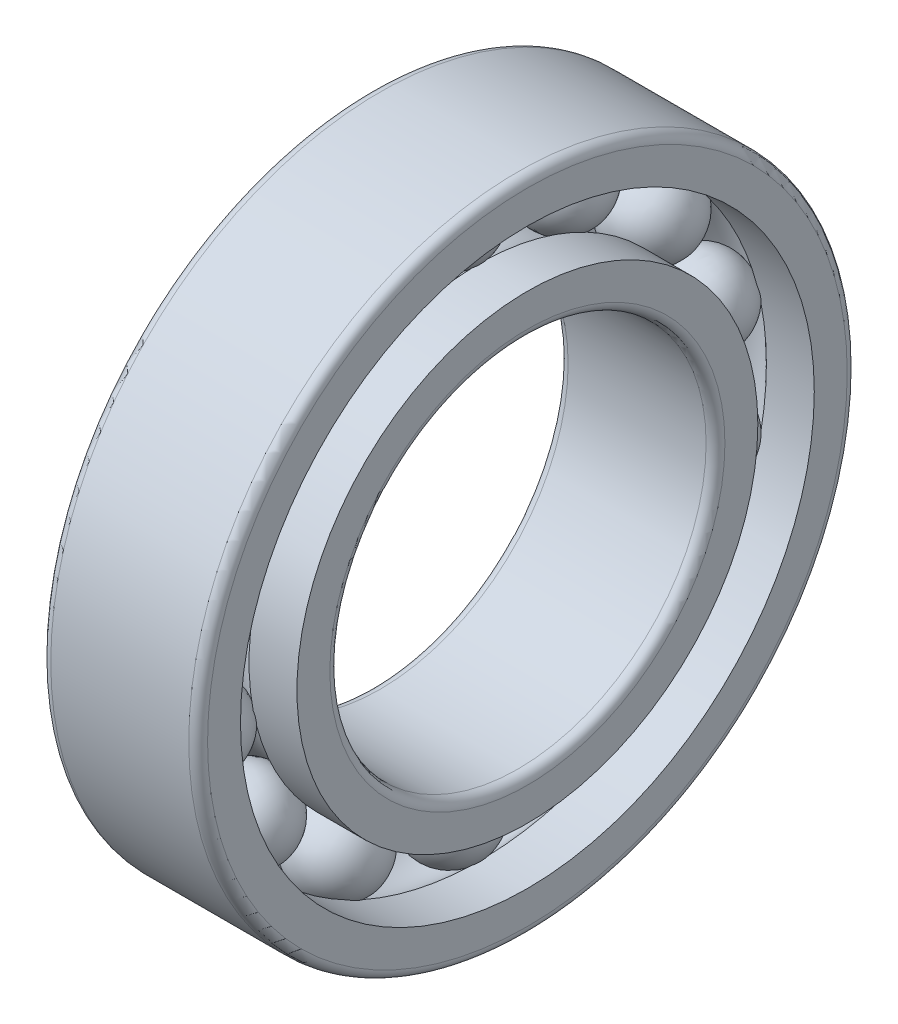
SolidWorks part; units mm, degrees
ref_plane "Plane1" through (0, 0, 0) normal (0, 0, 1) x (1, 0, 0)
ref_plane "Plane2" through (0, 0, 0) normal (0, 1, 0) x (1, 0, 0)
ref_plane "Plane3" through (0, 0, 0) normal (1, 0, 0) x (0, 0, -1)
sketch "Clipboard" plane through (0, 0, 0) normal (0, 0, 1) x (1, 0, 0)
  line L0 (-10, 0) -> (10, 0) construction
  line L1 (0, 0) -> (21.6965, -5.4095)
  line L2 (0, 0) -> (8.0049, 1.9959)
  line L3 (0, 0) -> (21.6965, -5.4095)
  line L4 (0, 0) -> (-22.3573, -0.3902)
  dimension "BallCLRad" = 8.25
sketch "CagSpiSke" plane through (0, 0, 0) normal (0, 0, 1) x (1, 0, 0)
  line L0 (0.135, 8.025) -> (0.135, 8.475)
  line L1 (0.135, 8.475) -> (-0.135, 8.475)
  line L2 (-0.135, 8.475) -> (-0.135, 8.025)
  line L3 (-0.135, 8.025) -> (0.135, 8.025)
  line L4 (-20.6375, 0) -> (20.6375, 0) construction
  line L5 (0, 0) -> (0, 23.7692) construction
  dimension "OD" = 16.95
  dimension "ID" = 16.05
revolve "CageSpine" add sketch "CagSpiSke" angle 0.001 about L4 reverse direction yes
ref_axis "Axis1" through (-50, 0, 0) along (1, 0, 0)
sketch "CagBalSke" plane through (0, 0, 0) normal (0, 0, 1) x (1, 0, 0)
  line L0 (-1.485, 8.25) -> (1.485, 8.25)
  line L1 (-1.905, 8.25) -> (1.905, 8.25) construction
  line L2 (-10, 0) -> (10, 0) construction
  line L3 (0, 0) -> (0, 24) construction
  arc A0 (1.485, 8.25) -> (-1.485, 8.25) centre (0, 8.25) cw
  dimension "BallCLRad" = 8.25
revolve "CageBall" [suppressed] add sketch "CagBalSke" angle 360 about L1 reverse direction yes
pattern_circular "CageBalls" [suppressed] count 14 every 25.714 about axis through (-50, 0, 0) along (1, 0, 0)
sketch "CagTrmODSke" plane through (0, 0, 0) normal (0, 0, 1) x (1, 0, 0)
  line L0 (1.486, 8.475) -> (1.486, 9.736)
  line L1 (1.486, 9.736) -> (-1.486, 9.736)
  line L2 (-1.486, 9.736) -> (-1.486, 8.475)
  line L3 (-1.486, 8.475) -> (1.486, 8.475)
  line L4 (-20.6375, 0) -> (20.6375, 0) construction
  line L5 (0, 0) -> (0, 25) construction
  dimension "Width" = 2.972
  dimension "ID" = 16.95
  dimension "OD" = 19.472
revolve "CageTrimOD" [suppressed] cut sketch "CagTrmODSke" angle 360 about L4 reverse direction yes
sketch "CagTrmIDSke" plane through (0, 0, 0) normal (0, 0, 1) x (1, 0, 0)
  line L0 (1.486, 6.766) -> (1.486, 8.025)
  line L1 (1.486, 8.025) -> (-1.486, 8.025)
  line L2 (-1.486, 8.025) -> (-1.486, 6.766)
  line L3 (-1.486, 6.766) -> (1.486, 6.766)
  line L4 (-20.6375, 0) -> (20.6375, 0) construction
  line L5 (0, 0) -> (0, 25) construction
  dimension "Width" = 2.972
  dimension "ID" = 13.532
  dimension "OD" = 16.05
revolve "CageTrimID" [suppressed] cut sketch "CagTrmIDSke" angle 360 about L4 reverse direction yes
sketch "BalSimSke" plane through (0, 0, 0) normal (0, 0, 1) x (1, 0, 0)
  line L0 (-10, 0) -> (10, 0) construction
  line L1 (-10, 8.25) -> (10, 8.25) construction
  line L2 (0, 0) -> (0, 23) construction
  circle A0 centre (0, 8.25) radius 1.35
  dimension "BallCLRad" = 8.25
  dimension "Ball_diameter" = 2.7
revolve "BallsSimplified" [suppressed] add sketch "BalSimSke" angle 360 about L0
sketch "BalDetSke" plane through (0, 0, 0) normal (0, 0, 1) x (1, 0, 0)
  line L0 (-1.35, 8.25) -> (1.35, 8.25)
  line L1 (-1.905, 8.25) -> (1.905, 8.25) construction
  line L2 (0, 0) -> (0, 25) construction
  arc A0 (1.35, 8.25) -> (-1.35, 8.25) centre (0, 8.25) cw
  dimension "BallCLRad" = 8.25
  dimension "Ball_diameter" = 2.7
revolve "BallDetailed" add sketch "BalDetSke" angle 360 about L1 reverse direction yes
sketch "InnRacSke" plane through (0, 0, 0) normal (0, 0, 1) x (1, 0, 0)
  line L0 (-0.9724, 7.35) -> (-2.5, 7.35)
  line L1 (-2.5, 7.35) -> (-2.5, 6.3)
  line L2 (-2.2, 6) -> (2.2, 6)
  line L3 (2.5, 6.3) -> (2.5, 7.35)
  line L4 (2.5, 7.35) -> (0.9724, 7.35)
  line L5 (-20.6375, 0) -> (20.6375, 0) construction
  line L6 (0, 0) -> (0, 30) construction
  arc A0 (-2.5, 6.3) -> (-2.2, 6) centre (-2.2, 6.3) ccw
  arc A1 (2.2, 6) -> (2.5, 6.3) centre (2.2, 6.3) ccw
  arc A2 (0.9724, 7.35) -> (-0.9724, 7.35) centre (0, 8.25) cw
  dimension "BallCLRad" = 8.25
  dimension "Fillet_radius" = 0.3
  dimension "Ball_diameter" = 2.65
  dimension "ID" = 12
  dimension "OD" = 14.7
  dimension "Width" = 5
revolve "InnerRace" add sketch "InnRacSke" angle 360 about L5 reverse direction yes
sketch "OutRacSke" plane through (0, 0, 0) normal (0, 0, 1) x (1, 0, 0)
  line L0 (-0.9724, 9.15) -> (-2.5, 9.15)
  line L1 (-2.5, 9.15) -> (-2.5, 10.2)
  line L2 (-2.2, 10.5) -> (2.2, 10.5)
  line L3 (2.5, 10.2) -> (2.5, 9.15)
  line L4 (2.5, 9.15) -> (0.9724, 9.15)
  line L5 (-20.6375, 0) -> (20.6375, 0) construction
  line L6 (0, 0) -> (0, 30) construction
  arc A0 (-2.5, 10.2) -> (-2.2, 10.5) centre (-2.2, 10.2) cw
  arc A1 (2.2, 10.5) -> (2.5, 10.2) centre (2.2, 10.2) cw
  arc A2 (0.9724, 9.15) -> (-0.9724, 9.15) centre (0, 8.25) ccw
  dimension "BallCLRad" = 8.25
  dimension "Fillet_radius" = 0.3
  dimension "Ball_diameter" = 2.65
  dimension "Width" = 5
revolve "OuterRace" add sketch "OutRacSke" angle 360 about L5 reverse direction yes
pattern_circular "BallsDetailed" count 14 every 25.714 about axis through (-50, 0, 0) along (1, 0, 0) of "BallDetailed"
equation "\"BallCLRad@Clipboard\" = ( \"OD@OutRacSke\" + \"ID@InnRacSke\" ) / 4"
equation "\"BallCLRad@BalSimSke\" = \"BallCLRad@Clipboard\""
equation "\"BallCLRad@BalDetSke\" = \"BallCLRad@Clipboard\""
equation "\"BallCLRad@InnRacSke\" = \"BallCLRad@Clipboard\""
equation "\"BallCLRad@OutRacSke\" = \"BallCLRad@Clipboard\""
equation "\"Ball_diameter@InnRacSke\" = \"Ball_diameter@BalDetSke\" - 0.05"
equation "\"Ball_diameter@OutRacSke\" = \"Ball_diameter@BalDetSke\" - 0.05"
equation "\"Ball_diameter@BalSimSke\" = \"Ball_diameter@BalDetSke\""
equation "\"Width@OutRacSke\" = \"Width@InnRacSke\""
equation "\"Fillet_radius@OutRacSke\" = \"Fillet_radius@InnRacSke\""
equation "\"Max_count@Clipboard\" = int( 3.14159265 / atn(( \"Ball_diameter@BalDetSke\" / 2) / sqr( \"BallCLRad@Clipboard\"  *  \"BallCLRad@Clipboard\" - ( \"Ball_diameter@BalDetSke\" / 2) *  ( \"Ball_diameter@BalDetSke\" / 2))))"
equation "\"Max_count@Clipboard\" = ((sgn( \"Max_count@Clipboard\" - \"Count@Clipboard\" )-1)*( \"Max_count@Clipboard\" - \"Count@Clipboard\" ))/-2+ \"Count@Clipboard\""
equation "\"Count@BallsDetailed\" = int( \"Show_count@Clipboard\" ) "
equation "\"Count@BallsDetailed\" = ((sgn( \"Count@BallsDetailed\" - \"Max_count@Clipboard\" )-1)*( \"Count@BallsDetailed\" - \"Max_count@Clipboard\" ))/-2+ \"Max_count@Clipboard\""
equation "\"Count@BallsDetailed\" = ((sgn( \"Count@BallsDetailed\" - \"Min_count@Clipboard\" )+1)*( \"Count@BallsDetailed\" - \"Min_count@Clipboard\"))/2 +\"Min_count@Clipboard\""
equation "\"Angle@BallsDetailed\" = 360.0 / \"Max_count@Clipboard\""
equation "\"BallCLRad@CagBalSke\" = \"BallCLRad@Clipboard\""
equation "\"Count@CageBalls\" = \"Count@BallsDetailed\""
equation "\"Angle@CageBalls\" = \"Angle@BallsDetailed\""
equation "\"Angle@CageSpine\" =  \"Angle@CageBalls\" * ( \"Count@CageBalls\" -1 + int( \"Count@CageBalls\" / \"Max_count@Clipboard\" ) )  + 0.001 -  int( \"Count@CageBalls\" / \"Max_count@Clipboard\" ) * 0.001"
equation "\"Angle@CageSpine\" =  \"Angle@CageSpine\" * int( \"Min_count@Clipboard\" / 2) + int(1 / \"Min_count@Clipboard\")  * 0.001"
equation "\"CageWallOD@CagBalSke\" =  \"Ball_diameter@BalDetSke\" * 1.1"
equation "\"Thickness@CagSpiSke\" =  \"Ball_diameter@BalDetSke\" * 0.1"
equation "\"OD@CagTrmODSke\" = \"BallCLRad@Clipboard\" * 2 + \"CageWallOD@CagBalSke\" + 0.002"
equation "\"ID@CagTrmODSke\" = \"BallCLRad@Clipboard\" * 2 + \"Ball_diameter@BalDetSke\" / 6"
equation "\"OD@CagTrmIDSke\" = \"BallCLRad@Clipboard\" * 2 - \"Ball_diameter@BalDetSke\" / 6"
equation "\"ID@CagTrmIDSke\" = \"BallCLRad@Clipboard\" * 2 - \"CageWallOD@CagBalSke\" + 0.002"
equation "\"OD@CagSpiSke\" = \"ID@CagTrmODSke\""
equation "\"ID@CagSpiSke\" = \"OD@CagTrmIDSke\""
equation "\"Width@CagTrmODSke\" = \"CageWallOD@CagBalSke\" + 0.002"
equation "\"Width@CagTrmIDSke\" = \"CageWallOD@CagBalSke\" + 0.002"
